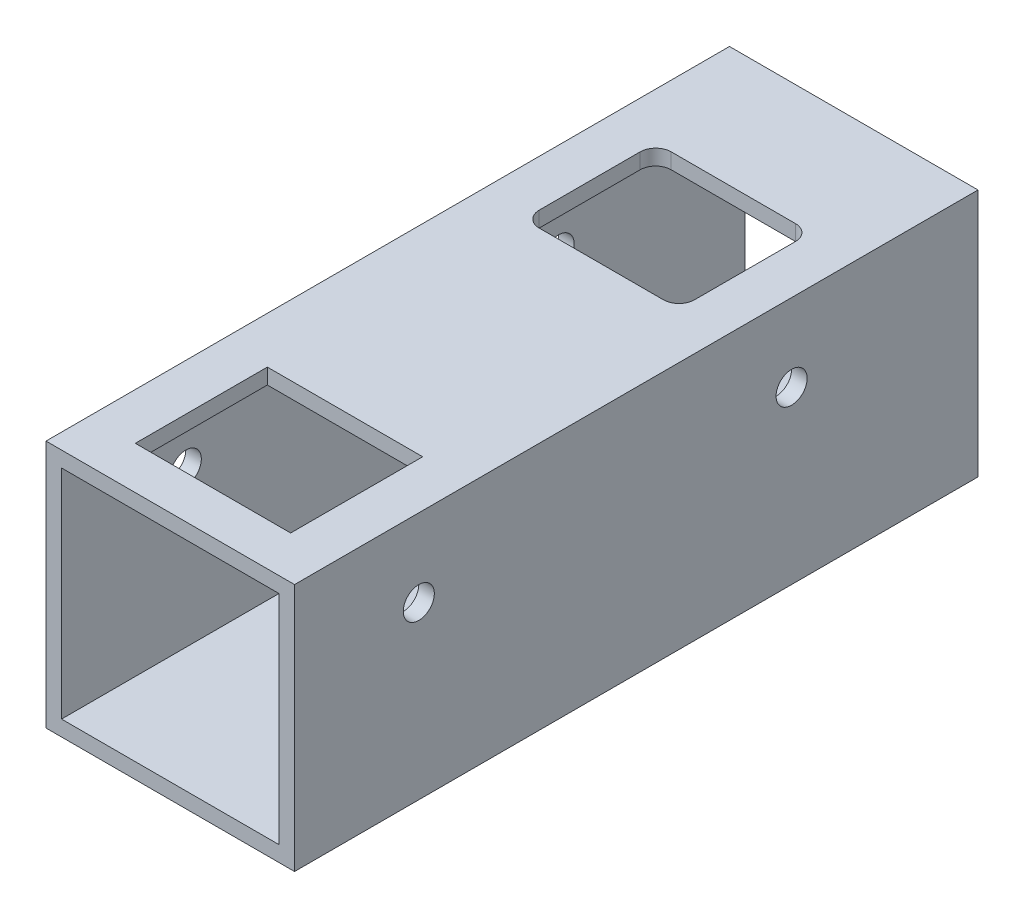
SolidWorks part; units mm, degrees
material "6061-T6 (SS)"
ref_plane "Front Plane" through (0, 0, 0) normal (0, 0, 1) x (1, 0, 0)
ref_plane "Top Plane" through (0, 0, 0) normal (0, 1, 0) x (1, 0, 0)
ref_plane "Right Plane" through (0, 0, 0) normal (1, 0, 0) x (0, 0, -1)
sketch "Sketch1" plane through (0, 0, 0) normal (0, 0, 1) x (1, 0, 0)
  line L1 (-25.4, -25.4) -> (25.4, -25.4)
  line L2 (-25.4, -25.4) -> (-25.4, 25.4)
  line L3 (-25.4, 25.4) -> (25.4, 25.4)
  line L4 (25.4, -25.4) -> (25.4, 25.4)
  line L5 (-25.4, -25.4) -> (25.4, 25.4) construction
  line L6 (-25.4, 25.4) -> (25.4, -25.4) construction
  point P0 (0, 0)
  dimension "D1" = 50.8
  dimension "D2" = 50.8
extrude "Boss-Extrude1" add sketch "Sketch1" along normal mid plane 139.7
shell "Shell1" thickness 3.175 removed face at (0, 0, -69.85) removed face at (0, 0, 69.85)
sketch "Sketch2" plane through (0, 0, 0) normal (0, 1, 0) x (1, 0, 0)
  line L0 (25.4, 69.85) -> (-25.4, 69.85) construction
  line L1 (15.875, 45.2437) -> (-15.875, 45.2437)
  line L2 (15.875, 45.2437) -> (15.875, 18.2563)
  line L3 (15.875, 18.2563) -> (-15.875, 18.2563)
  line L4 (-15.875, 45.2437) -> (-15.875, 18.2563)
  line L5 (25.4, -69.85) -> (-25.4, -69.85) construction
  line L7 (15.875, -34.1313) -> (-15.875, -34.1313)
  line L8 (15.875, -34.1313) -> (15.875, -61.1187)
  line L9 (15.875, -61.1187) -> (-15.875, -61.1187)
  line L10 (-15.875, -34.1313) -> (-15.875, -61.1187)
  point P4 (0, 45.2437)
  point P7 (0, 69.85)
  point P9 (15.875, 31.75)
  point P15 (0, -69.85)
  point P16 (0, -61.1187)
  point P17 (-15.875, -47.625)
  dimension "D1" = 31.75
  dimension "D2" = 26.9875
  dimension "D3" = 101.6
  dimension "D4" = 22.225
extrude "Cut-Extrude1" cut sketch "Sketch2" along normal through all
fillet "Fillet1" radius 3.175 4 edges at (15.875, 23.8125, -45.2437) (-15.875, 23.8125, -45.2437) (-15.875, 23.8125, -18.2563) (15.875, 23.8125, -18.2563)
sketch "Sketch3" plane through (0, 0, 0) normal (1, 0, 0) x (0, 0, -1)
  line L1 (-69.85, 25.4) -> (-69.85, -25.4) construction
  line L2 (-69.85, 25.4) -> (69.85, 25.4) construction
  circle A0 centre (31.75, 9.525) radius 3.175
  circle A1 centre (-44.45, 9.525) radius 3.175
  dimension "D1" = 6.35
  dimension "D2" = 25.4
  dimension "D3" = 76.2
  dimension "D4" = 15.875
extrude "Cut-Extrude2" cut sketch "Sketch3" against normal through all both and the other way through all
